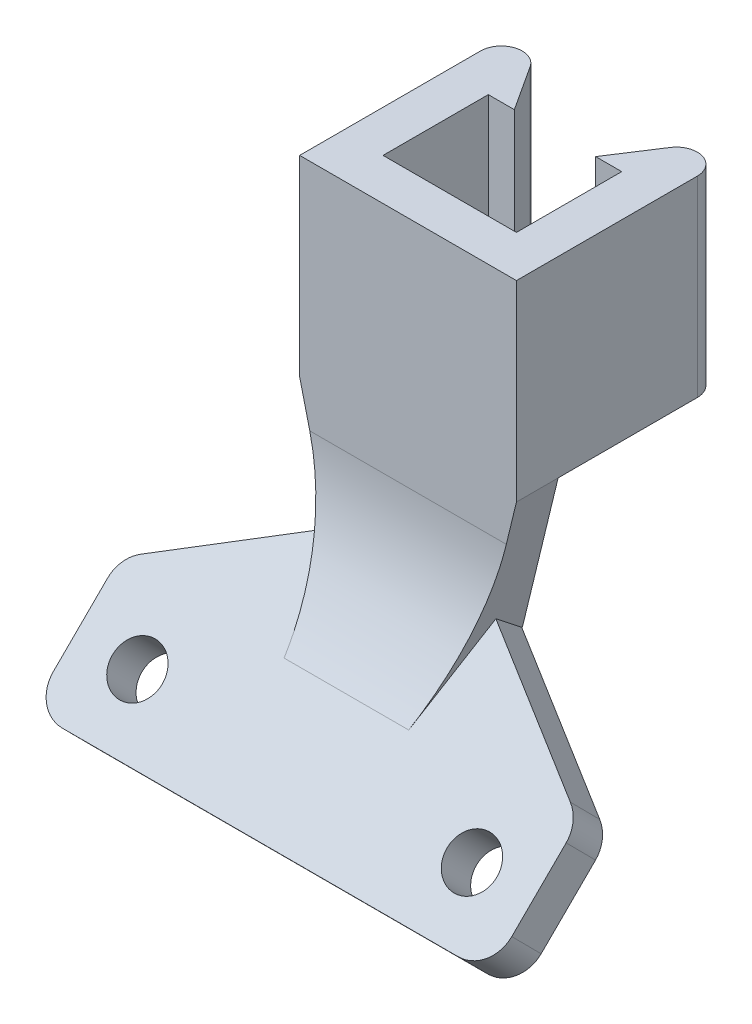
SolidWorks part; units mm, degrees
ref_plane "Front Plane" through (0, 0, 0) normal (0, 0, 1) x (1, 0, 0)
ref_plane "Top Plane" through (0, 0, 0) normal (0, 1, 0) x (1, 0, 0)
ref_plane "Right Plane" through (0, 0, 0) normal (1, 0, 0) x (0, 0, -1)
sketch "Sketch1" plane through (0, 0, 0) normal (1, 0, 0) x (0, 0, -1)
  line L1 (-2.55, 4.6) -> (2.55, 4.6)
  line L2 (-2.55, 4.6) -> (-2.55, -4.6)
  line L3 (-2.55, -4.6) -> (2.55, -4.6)
  line L4 (2.55, 4.6) -> (2.55, -4.6)
  line L5 (-2.55, 4.6) -> (2.55, -4.6) construction
  line L6 (-2.55, -4.6) -> (2.55, 4.6) construction
  point P0 (0, 0)
sketch "Sketch2" plane through (0, 0, 0) normal (1, 0, 0) x (0, 0, -1)
  line L0 (-2.5, -4.6) -> (-2.5, 4.6)
  line L1 (-4.4998, 4.6) -> (4.4998, 4.6)
  line L2 (-4.4998, 4.6) -> (-4.4998, -4.6)
  line L3 (-4.4998, -4.6) -> (4.4998, -4.6)
  line L4 (4.4998, 4.6) -> (4.4998, -4.6)
  line L5 (-4.4998, 4.6) -> (4.4998, -4.6) construction
  line L6 (-4.4998, -4.6) -> (4.4998, 4.6) construction
  line L7 (2.5, 4.6) -> (2.5, -4.6)
  line L8 (-2.5, 4.6) -> (2.5, 4.6) construction
  point P0 (0, 0)
extrude "Boss-Extrude1" add sketch "Sketch2" along normal blind 2 contours L4 L1 L2 L3 | L2 L1 L4 L3 region at (0, 0, 3.4999)
sketch "Sketch3" plane through (0, 0, 0) normal (-1, 0, 0) x (0, 0, 1)
  line L4 (-4.4998, 4.6) -> (-4.4998, -4.6)
  line L5 (-4.4998, -4.6) -> (4.4998, -4.6)
  line L7 (4.4998, 4.6) -> (-4.4998, 4.6)
  line L9 (-4.4998, -4.6) -> (4.4998, -4.6)
  line L11 (4.4998, 4.6) -> (-4.4998, 4.6)
  line L12 (-4.4998, 4.6) -> (-4.4998, -4.6)
  line L14 (4.4998, -4.6) -> (4.4998, 4.6)
  line L15 (4.4998, -4.6) -> (4.4998, 4.6)
  dimension "D1" = 0
extrude "Boss-Extrude2" add sketch "Sketch3" along normal blind 2 from offset 6.4 separate body
sketch "Sketch4" plane through (0, 0, 0) normal (-1, 0, 0) x (0, 0, 1)
  line L0 (2.5, 4.6) -> (2.5, -4.6) construction
  line L1 (2.5, 4.6) -> (2.5, -4.6)
  line L2 (2.5, 4.6) -> (4.4998, 4.6)
  line L3 (4.4998, 4.6) -> (4.4998, -4.6)
  line L4 (4.4998, -4.6) -> (2.5, -4.6)
extrude "Boss-Extrude3" add sketch "Sketch4" along normal blind 7
sketch "Sketch5" plane through (0, 4.6, 0) normal (0, 1, 0) x (1, 0, 0)
  line L0 (0, 2.55) -> (-1.25, 2.55)
  line L1 (0, -2.5) -> (0, 2.5) construction
  line L2 (0, 2.55) -> (2, 2.55)
  line L3 (2, -4.4998) -> (2, 4.4998) construction
  line L4 (2, 2.55) -> (2, 7.55)
  line L5 (-1.25, 2.55) -> (2, 7.55)
  line L6 (-3.2, -2.5) -> (-3.2, 0.8826) construction
  line L7 (-6.4, -2.5) -> (0, -2.5) construction
  line L8 (-6.4, 2.55) -> (-5.15, 2.55)
  line L9 (-6.4, 2.55) -> (-8.4, 2.55)
  line L10 (-8.4, 2.55) -> (-8.4, 7.55)
  line L11 (-5.15, 2.55) -> (-8.4, 7.55)
  line L12 (-8.4, 7.55) -> (2, 7.55)
  line L13 (-5.15, 2.55) -> (-1.25, 2.55)
  line M9 (2, 4.4998) -> (0, 4.4998)
  line M10 (0, 4.4998) -> (0, -2.5)
  line M12 (-6.4, -2.5) -> (-6.4, 4.4998)
  line M13 (-6.4, 4.4998) -> (-8.4, 4.4998)
extrude "Cut-Extrude2" cut sketch "Sketch5" against normal up to surface (9.2 mm away) contours L11 L13 L5 L12 M10 M9 M13 M12 | L5 M10 M9 | L11 M12 M13 region at (-3.2, 4.6, -5.4288) region at (0.0058, 4.6, -4.4909) region at (-6.4058, 4.6, -4.4909) up to face at (-3.2, -4.6, -0.5)
extrude "Boss-Extrude4" add sketch "Sketch5<3>" against normal up to surface (9.2 mm away) contours L8 L11 M12 | L11 L10 M13 | L5 L0 M10 | L5 L4 M9 region at (-0.4167, 4.6, -3.191) region at (-5.9833, 4.6, -3.191) region at (1.3391, 4.6, -5.5165) region at (-7.7391, 4.6, -5.5165) up to face at (-3.2, -4.6, -1.2946)
sketch "Sketch5<3>" plane through (0, 4.6, 0) normal (0, 1, 0) x (1, 0, 0) same geometry as "Sketch5"
fillet "Fillet1" radius 1 2 edges at (2, 0, -7.55) (-8.4, 0, -7.55)
sketch "Sketch9" plane through (0, 0, 4.4998) normal (0, 0, 1) x (1, 0, 0)
  line L0 (-3.2, -4.6) -> (-3.2, -11.6) construction
  line L1 (2, -4.6) -> (-8.4, -4.6) construction
  line L2 (-6.7, -11.6) -> (0.3, -11.6)
  line L3 (-6.7, -11.6) -> (-8.4, -4.6)
  line L4 (0.3, -11.6) -> (2, -4.6)
  line L5 (2, -4.6) -> (-8.4, -4.6)
  point P7 (-3.2, -11.6)
extrude "Boss-Extrude6" add sketch "Sketch9" against normal up to surface (1.9998 mm away) up to face at (-3.2, 0, 2.5)
sketch "Sketch10" plane through (0, 0, 0) normal (1, 0, 0) x (0, 0, -1)
  line L0 (-2.5, -11.6) -> (-8.8061, -17.8561)
sketch3d "3DSketch2"
  line L0 (0, -11.6, 2.5) -> (0, -17.8561, 8.8061) construction
  line L1 (0.3, -11.6, 2.5) -> (-6.7, -11.6, 2.5) construction
sketch "Sketch11" plane through (0, -4.5962, -4.5598) normal (0, 0.7099, 0.7043) x (1, 0, 0)
  line L0 (-3.2, -20.7629) -> (-3.2, -17.7629) construction
  line L1 (4.825, -17.7629) -> (-11.225, -17.7629) construction
  line L2 (6.3, -20.7629) -> (-12.7, -20.7629)
  line L3 (7.8, -19.2629) -> (7.8, -15.5878)
  line L4 (7.1035, -14.3211) -> (0.3, -10.0056)
  line L5 (0.3, -10.0056) -> (-6.7, -10.0056)
  line L6 (-14.2, -19.2629) -> (-14.2, -15.5878)
  line L7 (-13.5035, -14.3211) -> (-6.7, -10.0056)
  line L9 (0.3, -9.9445) -> (-6.7, -9.9445) construction
  line L10 (0.3, -9.9445) -> (-6.7, -9.9445)
  circle A0 centre (4.825, -17.7629) radius 1.2
  circle A1 centre (-11.225, -17.7629) radius 1.2
  arc A2 (-14.2, -15.5878) -> (-13.5035, -14.3211) centre (-12.7, -15.5878) cw
  arc A3 (-12.7, -20.7629) -> (-14.2, -19.2629) centre (-12.7, -19.2629) cw
  arc A4 (6.3, -20.7629) -> (7.8, -19.2629) centre (6.3, -19.2629) ccw
  arc A5 (7.8, -15.5878) -> (7.1035, -14.3211) centre (6.3, -15.5878) ccw
  point P5 (-3.2, -17.7629)
  point P12 (-3.2, -20.7629)
  dimension "D1" = 1.5
extrude "Boss-Extrude7" add sketch "Sketch11" along normal blind 2 contours L3 A5 L4 L5 L7 A2 L6 A3 L2 A4 A0 A1 region at (-3.2, -15.8338, 6.7676)
fillet "Fillet2" radius 10 1 edges at (-3.2, -10.7667, 4.4998)
sketch "Sketch13" plane through (0, 0, 2.5) normal (0, 0, -1) x (-1, 0, 0)
  line L0 (-0.3, -11.6) -> (-0.3, -11.643)
  line L1 (-0.3, -11.643) -> (6.7, -11.643)
  line L2 (6.7, -11.643) -> (6.7, -11.6)
  line L3 (6.7, -11.6) -> (-0.3, -11.6)
extrude "Boss-Extrude8" add sketch "Sketch13" against normal blind 1
